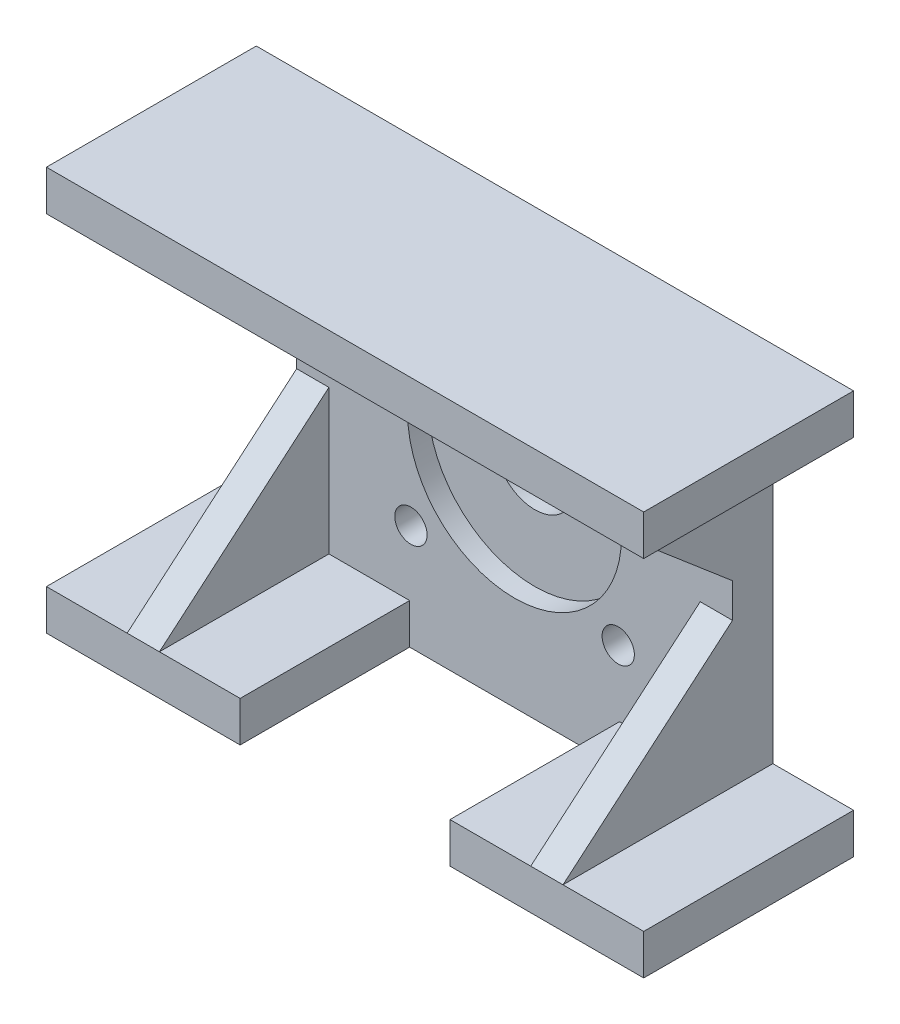
SolidWorks part; units mm, degrees
ref_plane "Front Plane" through (0, 0, 0) normal (0, 0, 1) x (1, 0, 0)
ref_plane "Top Plane" through (0, 0, 0) normal (0, 1, 0) x (1, 0, 0)
ref_plane "Right Plane" through (0, 0, 0) normal (1, 0, 0) x (0, 0, -1)
sketch "Sketch2" plane through (0, 0, 0) normal (0, 0, 1) x (1, 0, 0)
  line L0 (0, 0) -> (0, 25) construction
  line L1 (-27, 25) -> (27, 25)
  line L2 (-27, 25) -> (-27, -25)
  line L3 (-27, -25) -> (27, -25)
  line L4 (27, 25) -> (27, -25)
  line L5 (-27, 25) -> (27, -25) construction
  line L6 (-27, -25) -> (27, 25) construction
  line L7 (0, 0) -> (-27, 0) construction
  circle A0 centre (0, 0) radius 5
  circle A1 centre (-12.8408, 11.8896) radius 2
  circle A2 centre (-12.8408, -11.8896) radius 2
  circle A3 centre (12.8408, -11.8896) radius 2
  circle A4 centre (12.8408, 11.8896) radius 2
  circle A5 centre (0, 0) radius 17.5 construction
  point P0 (0, 0)
  dimension "D3" = 10
  dimension "D4" = 4
  dimension "D5" = 35
  dimension "D1" = 54
  dimension "D2" = 50
extrude "Boss-Extrude1" add sketch "Sketch2" along normal blind 5
sketch "Sketch3" plane through (0, 0, 5) normal (0, 0, 1) x (1, 0, 0)
  line L0 (27, 25) -> (-27, 25) construction
  line L1 (-37, 25) -> (37, 25)
  line L2 (-37, 25) -> (-37, 20)
  line L3 (-37, 20) -> (37, 20)
  line L4 (37, 25) -> (37, 20)
  line L5 (-37, 25) -> (37, 20) construction
  line L6 (-37, 20) -> (37, 25) construction
  line L7 (-27, 0) -> (27, 0) construction
  line L8 (-27, 25) -> (-27, -25) construction
  line L9 (27, -25) -> (27, 25) construction
  line L10 (-37, -20) -> (-13, -20)
  line L11 (37, -25) -> (37, -20)
  line L12 (-37, -25) -> (-13, -25)
  line L13 (-37, -25) -> (-37, -20)
  line L14 (-13, -20) -> (-13, -25)
  line L15 (0, 25) -> (0, -25) construction
  line L16 (-27, -25) -> (27, -25) construction
  line L17 (13, -20) -> (13, -25)
  line L18 (37, -20) -> (13, -20)
  line L19 (37, -25) -> (37, -20)
  line L20 (37, -25) -> (13, -25)
  point P0 (0, 22.5)
  line M14 (27, -25) -> (27, 25)
  line M15 (27, 25) -> (-27, 25)
  line M16 (-27, 25) -> (-27, -25)
  line M17 (-27, -25) -> (27, -25)
  dimension "D1" = 0
  dimension "D2" = 5
  dimension "D3" = 74
  dimension "D4" = 24
extrude "Boss-Extrude2" add sketch "Sketch3" along normal blind 21 contours L14 L10 M16 M17 | L13 L12 L10 M16 | L18 L17 M14 M17 | L20 L11 L18 M14 | L3 M16 M14 M15 | L2 L3 L1 M16 | L4 L1 L3 M14 region at (-32, 22.5, 5) region at (0, 22.5, 5) region at (32, 22.5, 5) region at (-32, -22.5, 5) region at (-20, -22.5, 5) region at (20, -22.5, 5) region at (32, -22.5, 5)
extrude "Boss-Extrude3" add sketch "Sketch3<3>" against normal blind 5 contours L4 L3 L2 L1
sketch "Sketch3<3>" plane through (0, 0, 5) normal (0, 0, 1) x (1, 0, 0) same geometry as "Sketch3"
extrude "Boss-Extrude4" add sketch "Sketch3<4>" against normal blind 5 contours L20 L11 L18 M14 | L13 L12 L10 M16 region at (32, -22.5, 5) region at (-32, -22.5, 5)
sketch "Sketch3<4>" plane through (0, 0, 5) normal (0, 0, 1) x (1, 0, 0) same geometry as "Sketch3"
sketch "Sketch4" plane through (0, 0, 5) normal (0, 0, 1) x (1, 0, 0)
  circle A0 centre (0, 0) radius 13.25
  dimension "D1" = 26.5
extrude "Cut-Extrude1" cut sketch "Sketch4" against normal blind 2.5
sketch "Sketch5" plane through (27, 0, 0) normal (1, 0, 0) x (0, 0, -1)
  line L0 (-26, 20) -> (-5, 2.1268)
  line L1 (-5, -20) -> (-5, 20) construction
  line L2 (0, 0) -> (-5, 0) construction
  line L3 (-26, 20) -> (-5, 20)
  line L4 (-5, 20) -> (-5, 2.1268)
  line L5 (0, -20) -> (-5, -20) construction
  line L6 (-26, -20) -> (-5, -20)
  line L7 (-26, -20) -> (-5, -2.1268)
  line L8 (-5, -20) -> (-5, -2.1268)
  dimension "D2" = 22.1268
extrude "Boss-Extrude7" add sketch "Sketch5" against normal blind 4
extrude "Boss-Extrude8" add sketch "Sketch5<2>" against normal blind 4 from offset 50 offset against normal yes
sketch "Sketch5<2>" plane through (27, 0, 0) normal (1, 0, 0) x (0, 0, -1) same geometry as "Sketch5"
